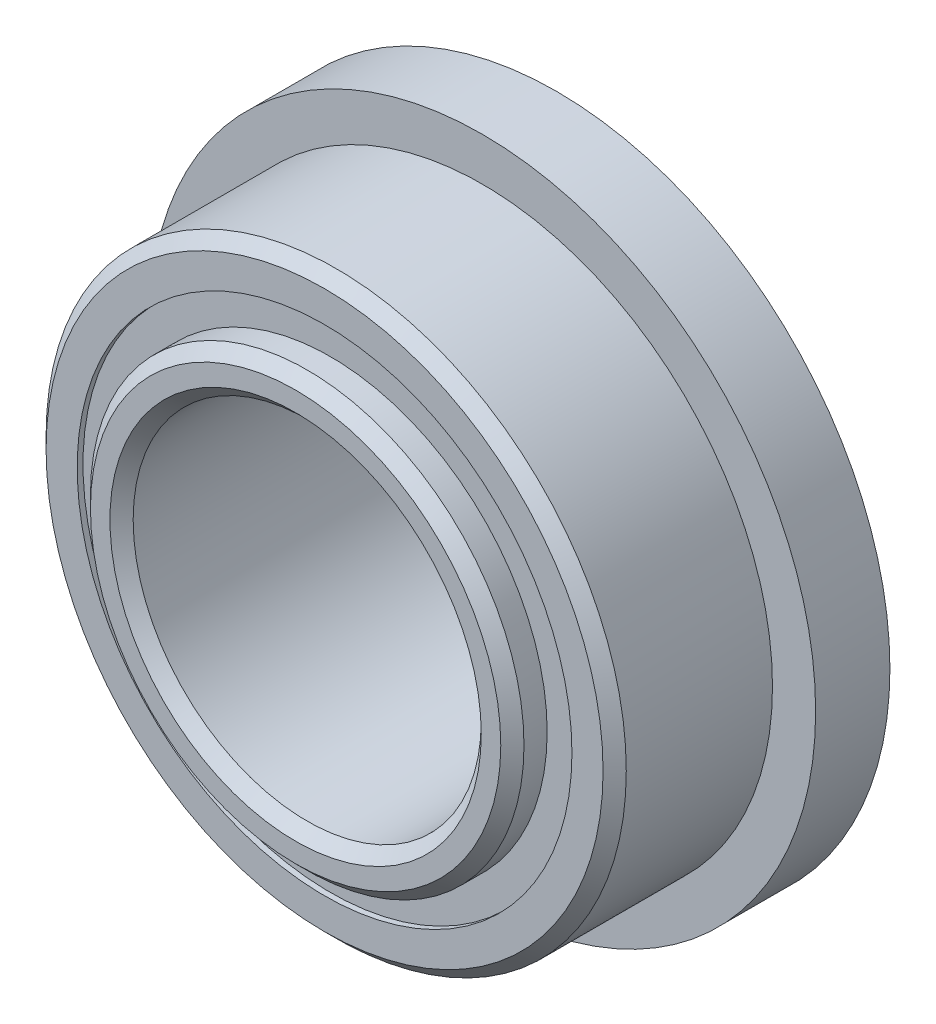
SolidWorks part; units mm, degrees
ref_plane "Front Plane" through (0, 0, 0) normal (0, 0, 1) x (1, 0, 0)
ref_plane "Top Plane" through (0, 0, 0) normal (0, 1, 0) x (1, 0, 0)
ref_plane "Right Plane" through (0, 0, 0) normal (1, 0, 0) x (0, 0, -1)
sketch "Sketch1" plane through (0, 0, 0) normal (1, 0, 0) x (0, 0, -1)
  line L0 (-1.5875, 0) -> (1.5875, 0) construction
  line L1 (0, 3.9688) -> (0, -3.9688) construction
  line L2 (1.4288, 3.9688) -> (-1.4288, 3.9688)
  line L3 (-1.4288, 3.9688) -> (-1.5875, 3.81)
  line L4 (-1.5875, 3.81) -> (-1.5875, 3.3843)
  line L5 (-1.5875, 3.3843) -> (-0.7056, 3.3843)
  line L6 (1.5875, 3.3843) -> (0.7056, 3.3843)
  line L7 (1.5875, 3.81) -> (1.5875, 3.3843)
  line L8 (1.4288, 3.9688) -> (1.5875, 3.81)
  line L9 (0, 3.9688) -> (0, 3.175) construction
  line L10 (0, 3.175) -> (0, 2.3813) construction
  arc A0 (-0.7056, 3.3843) -> (0.7056, 3.3843) centre (0, 3.175) cw
  point P14 (0, 2.3813)
  dimension "D3" = 1.4111
  dimension "D1" = 45
  dimension "Width" = 3.175
  dimension "OD" = 7.9375
  dimension "D2" = 0.1588
  dimension "Shaft Dia" = 4.7625
  dimension "D4" = 0.2093
revolve "Revolve1" add sketch "Sketch1" angle 360 about L0
sketch "Sketch3" plane through (0, 0, 0) normal (1, 0, 0) x (0, 0, -1)
  line L0 (-0.7056, 2.9657) -> (-1.9837, 2.9657) construction
  line L1 (-1.5875, 3.81) -> (-1.5875, 3.3843) construction
  line L2 (-1.4288, 3.9688) -> (-1.5875, 3.81) construction
  line L3 (-1.9837, 2.9657) -> (-1.9837, 2.54) construction
  line L4 (-1.9837, 2.54) -> (-1.9837, 2.8069)
  line L5 (-1.9837, 2.54) -> (-1.825, 2.3813)
  line L6 (-1.825, 2.3813) -> (1.825, 2.3813)
  line L8 (1.825, 2.3813) -> (1.9837, 2.54)
  line L10 (1.9837, 2.54) -> (1.9837, 2.9657) construction
  line L11 (1.9837, 2.9657) -> (0.7056, 2.9657) construction
  line L12 (0, 3.9688) -> (0, -3.9688) construction
  line L13 (1.4288, 3.9688) -> (1.5875, 3.81) construction
  line L14 (-1.9837, 2.8069) -> (-1.825, 2.9657)
  line L15 (-1.825, 2.9657) -> (-0.7056, 2.9657)
  line L16 (0.7056, 2.9657) -> (1.825, 2.9657)
  line L17 (1.825, 2.9657) -> (1.9837, 2.8069)
  line L18 (1.9837, 2.8069) -> (1.9837, 2.54)
  arc A1 (0.7056, 2.9657) -> (-0.7056, 2.9657) centre (0, 3.175) cw
  arc A2 (0.7056, 3.3843) -> (-0.7056, 3.3843) centre (0, 3.175) ccw construction
  dimension "D1" = 45
  dimension "Ring Wd" = 3.9675
revolve "Revolve3" add sketch "Sketch3" angle 360 about L0
sketch "Sketch4" plane through (0, 0, 0) normal (1, 0, 0) x (0, 0, -1)
  line L0 (-0.736, 3.175) -> (0.736, 3.175)
  arc A2 (-0.736, 3.175) -> (0.736, 3.175) centre (0, 3.175) cw
  arc A3 (0.7056, 3.3843) -> (-0.7056, 3.3843) centre (0, 3.175) ccw construction
revolve "Revolve4" add sketch "Sketch4" angle 360 about L0
ref_axis "Axis1" through (0, 0, -1.5875) along (0, 0, 1)
pattern_circular "CirPattern1" count 10 every 36 about axis through (0, 0, -1.5875) along (0, 0, 1) of bodies 104
sketch "Sketch5" plane through (0, 0, 0) normal (1, 0, 0) x (0, 0, -1)
  line L0 (-1.5875, 3.3843) -> (-0.7056, 3.3843) construction
  line L1 (-1.5081, 3.3843) -> (-0.736, 3.3843)
  line L2 (-1.5081, 3.3843) -> (-1.5081, 2.9657)
  line L3 (-1.5081, 2.9657) -> (-0.736, 2.9657)
  line L4 (-0.736, 3.3843) -> (-0.736, 2.9657)
  line L5 (-0.7056, 2.9657) -> (-1.9837, 2.9657) construction
  line L6 (1.5875, 3.3843) -> (0.7056, 3.3843) construction
  line L7 (1.5081, 3.3843) -> (0.736, 3.3843)
  line L8 (1.5081, 3.3843) -> (1.5081, 2.9657)
  line L9 (1.5081, 2.9657) -> (0.736, 2.9657)
  line L10 (0.736, 3.3843) -> (0.736, 2.9657)
  line L11 (1.9837, 2.9657) -> (0.7056, 2.9657) construction
  line L12 (-1.4288, 3.9688) -> (-1.5875, 3.81) construction
  point P18 (-1.5081, 3.8894)
revolve "Revolve5" add sketch "Sketch5" angle 360 about L0
sketch "Sketch6" plane through (0, 0, 0) normal (1, 0, 0) x (0, 0, -1)
  line L1 (1.5875, 3.3843) -> (0.5715, 3.3843)
  line L2 (1.5875, 3.3843) -> (1.5875, 4.5593)
  line L3 (1.5875, 4.5593) -> (0.5715, 4.5593)
  line L4 (0.5715, 3.3843) -> (0.5715, 4.5593)
  line L5 (1.5875, 0) -> (-1.5875, 0) construction
  dimension "Flange OD" = 9.1186
  dimension "Th" = 1.016
revolve "Revolve6" add sketch "Sketch6" angle 360 about L5
equation "\"D2@Sketch1\" = \"Width@Sketch1\"*.05"
equation "\"D3@Sketch1\" = \"Width@Sketch1\"/2.25"
equation "\"D4@Sketch1\" = (((\"OD@Sketch1\"-\"Width@Sketch1\")/2)/3.25)/3.5"
equation "\"D2@CirPattern1\" = 360/\"Balls@CirPattern1\""
